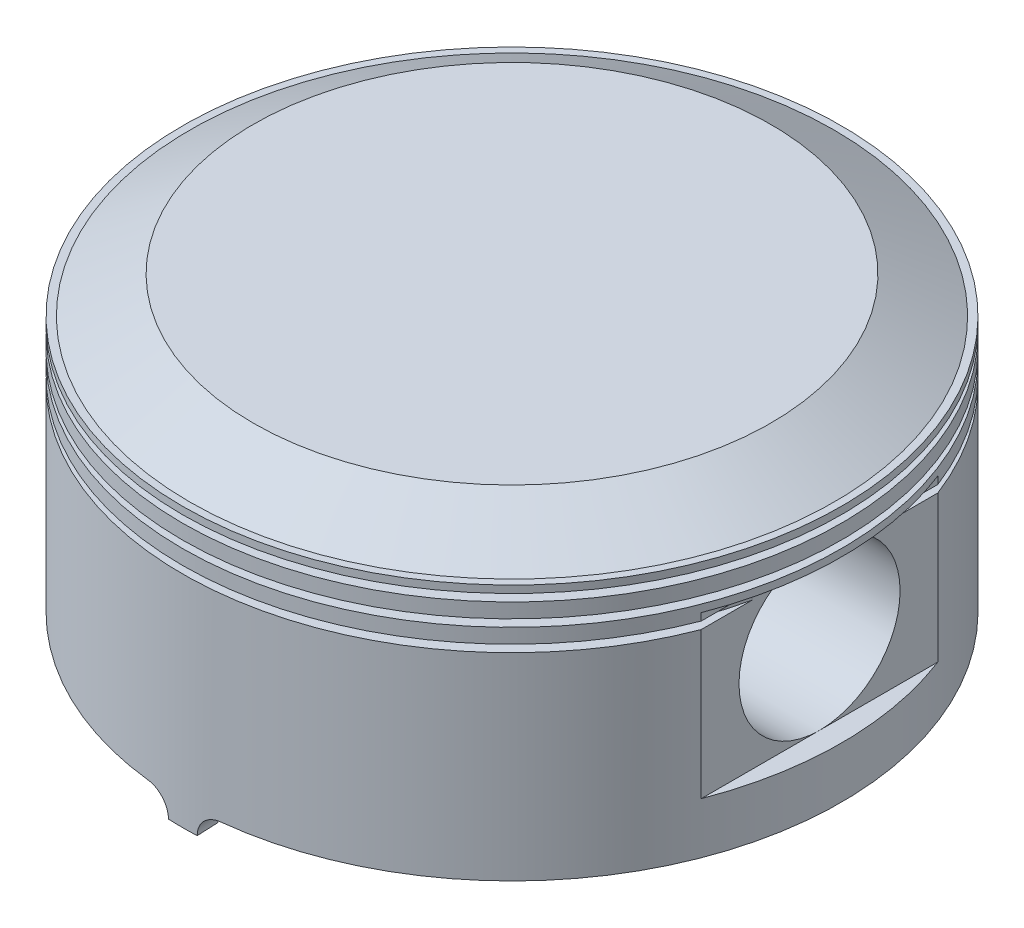
SolidWorks part; units mm, degrees
ref_plane "Front Plane" through (0, 0, 0) normal (0, 0, 1) x (1, 0, 0)
ref_plane "Top Plane" through (0, 0, 0) normal (0, 1, 0) x (1, 0, 0)
ref_plane "Right Plane" through (0, 0, 0) normal (1, 0, 0) x (0, 0, -1)
sketch "Piston CS" plane through (0, 0, 0) normal (0, 0, 1) x (1, 0, 0)
  line L0 (0, 0) -> (0, -5)
  line L1 (0, -5) -> (23.005, -5)
  line L2 (23.005, -5) -> (37, -13.08)
  line L3 (37, -13.08) -> (37, -23.08)
  line L4 (37, -23.08) -> (42, -23.08)
  line L5 (42, -23.08) -> (42, -40)
  line L6 (42, -40) -> (45, -40)
  line L8 (44, -5) -> (35.3397, 0)
  line L9 (35.3397, 0) -> (0, 0)
  line L10 (44, -5) -> (45, -5)
  line L12 (45, -5) -> (45, -40)
  dimension "D1" = 5
  dimension "D2" = 5
  dimension "D3" = 3
  dimension "D4" = 45
  dimension "D5" = 10
  dimension "D6" = 35
  dimension "D7" = 5
  dimension "D8" = 30
  dimension "D9" = 1
  dimension "D10" = 16.92
revolve "Revolve1" add sketch "Piston CS" angle 360 about L0
sketch "Sketch5" plane through (0, -40, 0) normal (0, -1, 0) x (1, 0, 0)
  line L0 (0, -68.5184) -> (0, 57.0205) construction
  line L1 (-73.4461, 0) -> (71.8036, 0) construction
  line L2 (-24.1039, -38) -> (-24.1039, -15)
  line L3 (-24.1039, -15) -> (-14.1039, -15)
  line L4 (-14.1039, -15) -> (-14.1039, 15)
  line L5 (-24.1039, 15) -> (-14.1039, 15)
  line L6 (-24.1039, 38) -> (-24.1039, 15)
  line L7 (24.1039, 38) -> (24.1039, 15)
  line L8 (24.1039, 15) -> (14.1039, 15)
  line L9 (14.1039, -15) -> (14.1039, 15)
  line L10 (24.1039, -15) -> (14.1039, -15)
  line L11 (24.1039, -38) -> (24.1039, -15)
  arc A2 (-24.1039, 38) -> (-24.1039, -38) centre (0, 0) ccw
  arc A3 (24.1039, 38) -> (24.1039, -38) centre (0, 0) cw
  point P10 (-14.1039, 0)
  point P19 (14.1039, 0)
  dimension "D1" = 23
  dimension "D2" = 10
  dimension "D3" = 15
extrude "Boss-Extrude1" add sketch "Sketch5" against normal up to next
sketch "Gudgeon Hole" plane through (-14.1039, 0, 0) normal (1, 0, 0) x (0, 0, -1)
  line L0 (35.3397, 0) -> (-35.3397, 0) construction
  circle A0 centre (0, -22) radius 11
  dimension "Gudgeon_Diameter" = 22
  dimension "Gudgeon_Offset" = 22
extrude "Cut-Extrude1" cut sketch "Gudgeon Hole" against normal through all and the other way through all
ref_plane "Plane1" through (0, 0, 45) normal (0, 0, 1) x (1, 0, 0)
sketch "Gudgeon Hole Cutouts" plane through (0, 0, 45) normal (0, 0, 1) x (1, 0, 0)
  line L0 (45, -33) -> (42, -33)
  line L1 (-45, -5) -> (-45, -11) construction
  line L3 (-45, -10.9714) -> (-45, -11)
  line L4 (42, -23.08) -> (42, -40) construction
  line L5 (42, -33) -> (42, -11)
  line L8 (-45, -10.9714) -> (-42, -10.9714)
  line L9 (-42, -10.9714) -> (-42, -33)
  line L11 (0, 0) -> (0, -52.5828) construction
  line L12 (35.3397, 0) -> (-35.3397, 0) construction
  line L14 (42, -11) -> (45, -11)
  line L15 (-42, -33) -> (-45, -33)
  spline S0 degree 2 poles (-45, -11) (-42.3111, -22) (-45, -33) knots 0 0 0 1 1 1 weights 0.034 0.045 0.056 construction
  spline S1 degree 2 poles (-45, -11) (-42.3111, -22) (-45, -33) knots 0 0 0 1 1 1 weights 0.034 0.045 0.056
  spline S2 degree 2 poles (45, -33) (42.3111, -22) (45, -11) knots 0 0 0 1 1 1 weights 0.034 0.045 0.056 construction
  spline S3 degree 2 poles (45, -33) (42.3111, -22) (45, -11) knots 0 0 0 1 1 1 weights 0.034 0.045 0.056
  dimension "D1" = 3
extrude "Cut-Extrude2" cut sketch "Gudgeon Hole Cutouts" against normal through all contours L3 S1 L9 L8 | S3 region at (43.0861, -22, 45) region at (-43.0869, -21.9795, 45)
sketch "Ring CS" plane through (0, 0, 0) normal (0, 0, 1) x (1, 0, 0)
  line L0 (44, -5) -> (45, -5) construction
  line L1 (45, -6) -> (43, -6)
  line L2 (45, -6) -> (45, -7)
  line L3 (45, -7) -> (43, -7)
  line L4 (43, -6) -> (43, -7)
  line L5 (45, -5) -> (45, -40) construction
  line L6 (45, -9) -> (43, -9)
  line L7 (43, -9) -> (43, -10)
  line L8 (45, -10) -> (43, -10)
  line L9 (45, -9) -> (45, -10)
  line L10 (45, -12) -> (43, -12)
  line L11 (43, -12) -> (43, -13)
  line L12 (45, -13) -> (43, -13)
  line L13 (45, -12) -> (45, -13)
  dimension "D1" = 3
  dimension "Groove_Offset" = 1
  dimension "Groove_Depth" = 2
  dimension "Groove_Height" = 1
  dimension "Groove_Spacing" = 3
revolve "Cut-Revolve1" cut sketch "Ring CS" angle 360 about L0
sketch "Sketch9" plane through (0, -40, 0) normal (0, -1, 0) x (1, 0, 0)
  line L0 (0, 54.5291) -> (0, 42) construction
  line L1 (-49.8964, 0) -> (45, 0) construction
  line L2 (-1.832, 41.96) -> (-1.9629, 44.9572)
  line L3 (1.832, 41.96) -> (1.9629, 44.9572)
  line L4 (1.832, 41.96) -> (1.9629, 44.9572) construction
  line L5 (-1.832, 41.96) -> (-1.9629, 44.9572) construction
  line L6 (1.832, -41.96) -> (1.9629, -44.9572) construction
  line L7 (-1.832, -41.96) -> (-1.9629, -44.9572) construction
  line L8 (1.832, -41.96) -> (1.9629, -44.9572)
  line L9 (-1.832, -41.96) -> (-1.9629, -44.9572)
  line L10 (0, -42) -> (0, -45) construction
  arc A0 (-24.1039, -34.3948) -> (24.1039, -34.3948) centre (0, 0) ccw construction
  arc A1 (24.1039, 34.3948) -> (-24.1039, 34.3948) centre (0, 0) ccw construction
  circle A2 centre (0, 0) radius 45 construction
  arc A3 (-1.832, -41.96) -> (1.832, -41.96) centre (0, 0) ccw
  arc A4 (1.832, 41.96) -> (-1.832, 41.96) centre (0, 0) ccw
  arc A5 (-1.9629, -44.9572) -> (1.9629, -44.9572) centre (0, 0) ccw
  arc A6 (1.9629, 44.9572) -> (-1.9629, 44.9572) centre (0, 0) ccw
  point P16 (0, 0)
  point P17 (0, 0)
  point P18 (0, 0)
  dimension "D1" = 2.5
  dimension "D2" = 5
extrude "Boss-Extrude2" add sketch "Sketch9" along normal blind 3
fillet "Fillet1" radius 3 4 edges at (-1.8974, -40, 43.4586) (1.8974, -40, 43.4586) (1.8974, -40, -43.4586) (-1.8974, -40, -43.4586)
